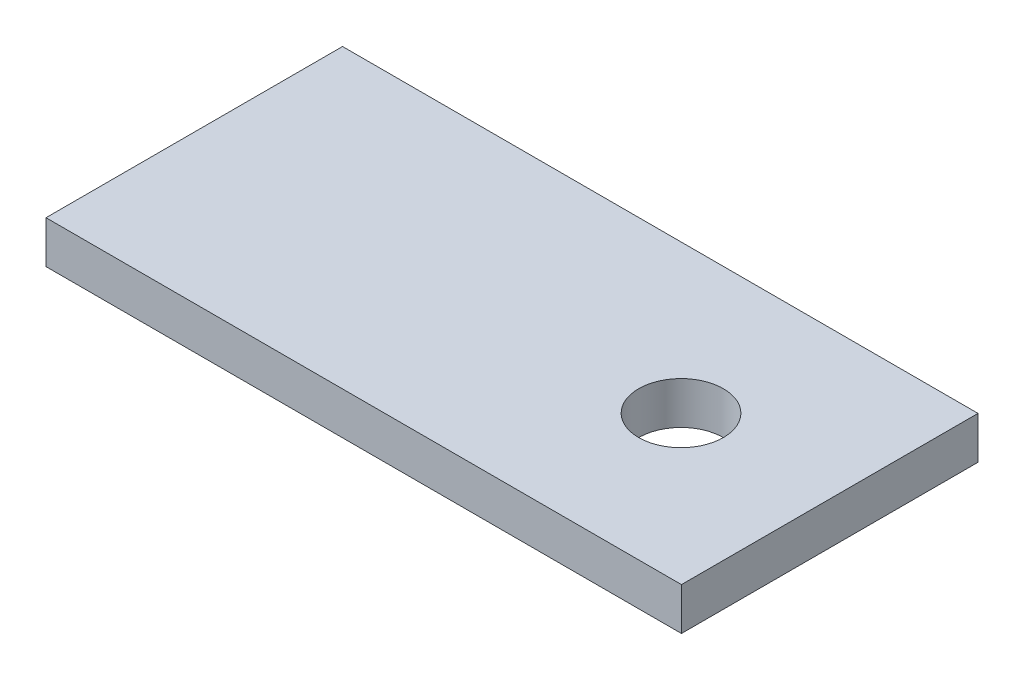
SolidWorks part; units mm, degrees
ref_plane "Front" through (0, 0, 0) normal (0, 0, 1) x (1, 0, 0)
ref_plane "Top" through (0, 0, 0) normal (0, 1, 0) x (1, 0, 0)
ref_plane "Right" through (0, 0, 0) normal (1, 0, 0) x (0, 0, -1)
sketch "Sketch1" plane through (0, 0, 0) normal (0, 1, 0) x (1, 0, 0)
  line L0 (-30, 0) -> (0, 0)
  line L2 (0, 0) -> (0, 14)
  line L3 (0, 14) -> (-30, 14)
  line L4 (-30, 0) -> (-30, 14)
  line L5 (0, 0) -> (-30, 14) construction
  line L6 (0, 14) -> (-30, 0) construction
  circle A0 centre (-7.0204, 7) radius 2
  point P4 (-15, 7)
  dimension "D1" = 30
  dimension "D2" = 14
extrude "Boss-Extrude1" add sketch "Sketch1" along normal blind 2 contours L3 L4 L0 L2
extrude "Cut-Extrude10" cut sketch "Sketch1<9>" against normal through all and the other way through all flip side to cut
sketch "Sketch1<9>" plane through (0, 0, 0) normal (0, 1, 0) x (1, 0, 0) same geometry as "Sketch1"
